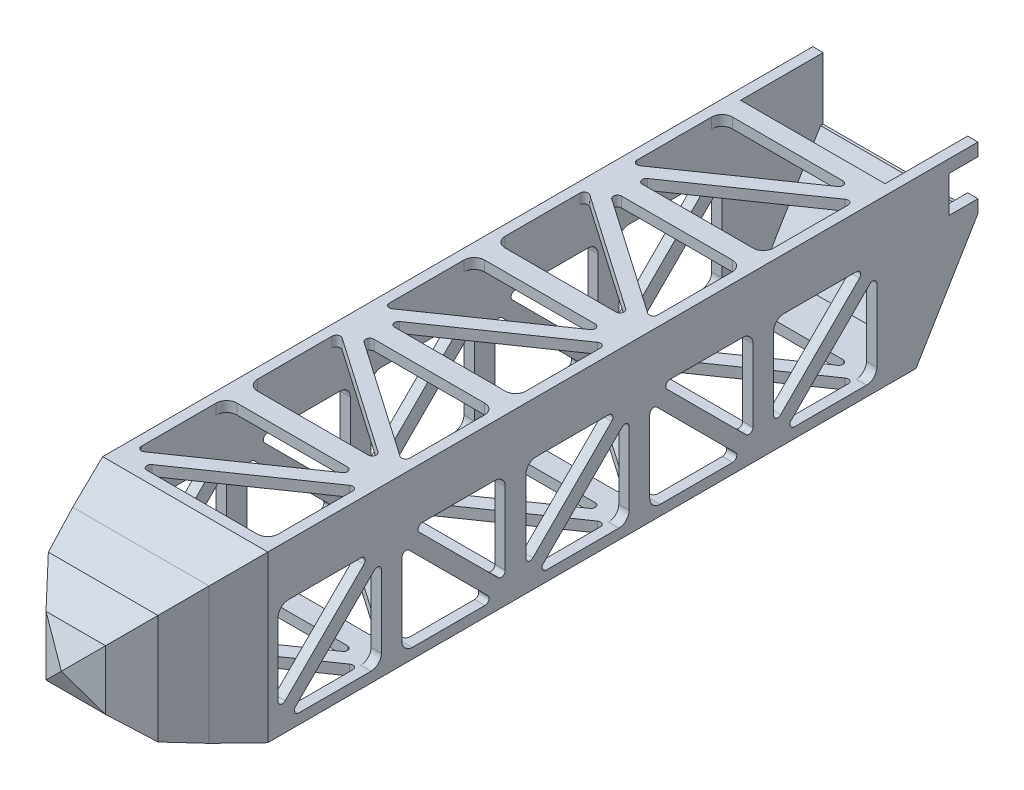
SolidWorks part; units mm, degrees
material "Balsa"
ref_plane "Front Plane" through (0, 0, 0) normal (0, 0, 1) x (1, 0, 0)
ref_plane "Top Plane" through (0, 0, 0) normal (0, 1, 0) x (1, 0, 0)
ref_plane "Right Plane" through (0, 0, 0) normal (1, 0, 0) x (0, 0, -1)
sketch "Sketch1" plane through (0, 0, 0) normal (0, 0, 1) x (1, 0, 0)
  line L1 (-50.8, -50.8) -> (50.8, -50.8)
  line L2 (-50.8, -50.8) -> (-50.8, 50.8)
  line L3 (-50.8, 50.8) -> (50.8, 50.8)
  line L4 (50.8, -50.8) -> (50.8, 50.8)
  line L5 (-50.8, -50.8) -> (50.8, 50.8) construction
  line L6 (-50.8, 50.8) -> (50.8, -50.8) construction
  point P0 (0, 0)
  dimension "D1" = 101.6
extrude "Boss-Extrude1" add sketch "Sketch1" along normal blind 436.88 contours L2 L1 L4 L3
ref_plane "Plane1" through (0, 0, 464.1566) normal (0, 0, 1) x (1, 0, 0)
sketch "Sketch3" plane through (0, 0, 464.1566) normal (0, 0, 1) x (1, 0, 0)
  line L1 (-41.9373, -41.9373) -> (41.9373, -41.9373)
  line L2 (-41.9373, -41.9373) -> (-41.9373, 41.9373)
  line L3 (-41.9373, 41.9373) -> (41.9373, 41.9373)
  line L4 (41.9373, -41.9373) -> (41.9373, 41.9373)
  line L5 (-41.9373, -41.9373) -> (41.9373, 41.9373) construction
  line L6 (-41.9373, 41.9373) -> (41.9373, -41.9373) construction
  point P0 (0, 0)
  dimension "D1" = 83.8746
  dimension "D2" = 83.8746
sketch "Sketch5" plane through (0, 0, 436.88) normal (0, 0, 1) x (1, 0, 0)
  line L0 (50.8, -50.8) -> (50.8, 50.8) construction
  line L1 (-50.8, 50.8) -> (50.8, 50.8) construction
  line L2 (-50.8, -50.8) -> (-50.8, 50.8) construction
  line L3 (-50.8, -50.8) -> (50.8, -50.8) construction
  line L4 (50.8, -50.8) -> (50.8, 50.8)
  line L5 (-50.8, 50.8) -> (50.8, 50.8)
  line L6 (-50.8, -50.8) -> (-50.8, 50.8)
  line L7 (-50.8, -50.8) -> (50.8, -50.8)
  dimension "D1" = 101.6
  dimension "D2" = 101.6
loft "Loft2" add profiles "Sketch5", "Sketch3" connector at (-50.8, 50.8, 436.88) connector at (-41.9373, 41.9373, 464.1566)
ref_plane "Plane2" through (0, 0, 487.3594) normal (0, 0, 1) x (1, 0, 0)
sketch "Sketch6" plane through (0, 0, 487.3594) normal (0, 0, 1) x (1, 0, 0)
  line L1 (-33.716, -33.716) -> (33.716, -33.716)
  line L2 (-33.716, -33.716) -> (-33.716, 33.716)
  line L3 (-33.716, 33.716) -> (33.716, 33.716)
  line L4 (33.716, -33.716) -> (33.716, 33.716)
  line L5 (-33.716, -33.716) -> (33.716, 33.716) construction
  line L6 (-33.716, 33.716) -> (33.716, -33.716) construction
  point P0 (0, 0)
loft "Loft3" add profiles "Sketch3<6>", "Sketch6" connector at (-41.9373, 41.9373, 464.1566) connector at (-33.716, 33.716, 487.3594)
sketch "Sketch3<6>" plane through (0, 0, 464.1566) normal (0, 0, 1) x (1, 0, 0) same geometry as "Sketch3"
ref_plane "Plane3" through (0, 0, 504.2173) normal (0, 0, 1) x (1, 0, 0)
sketch "Sketch7" plane through (0, 0, 504.2173) normal (0, 0, 1) x (1, 0, 0)
  line L5 (-41.9373, -41.9373) -> (41.9373, 41.9373) construction
  line L6 (-18.3041, -18.3041) -> (18.3041, -18.3041)
  line L8 (-18.3041, -18.3041) -> (-18.3041, 18.3041)
  line L9 (-18.3041, 18.3041) -> (18.3041, 18.3041)
  line L10 (18.3041, -18.3041) -> (18.3041, 18.3041)
  line L11 (-18.3041, -18.3041) -> (18.3041, 18.3041) construction
  line L12 (-18.3041, 18.3041) -> (18.3041, -18.3041) construction
  point P1 (0, 0)
loft "Loft4" add profiles "Sketch6<4>", "Sketch7" connector at (33.716, 33.716, 487.3594) connector at (18.3041, 18.3041, 504.2173)
sketch "Sketch6<4>" plane through (0, 0, 487.3594) normal (0, 0, 1) x (1, 0, 0) same geometry as "Sketch6"
sketch3d "3DSketch1" plane through (0, 0, 0) normal (0, 0, 1) x (1, 0, 0)
  dimension "D1" = 8.8627
sketch "Sketch8" plane through (0, 0, 513.08) normal (0, 0, 1) x (1, 0, 0)
  point P0 (0, 0)
loft "Loft5" add profiles "Sketch8", "Sketch7<5>"
sketch "Sketch7<5>" plane through (0, 0, 504.2173) normal (0, 0, 1) x (1, 0, 0) same geometry as "Sketch7"
shell "Shell1" thickness 6.35 removed face at (0, 0, 0)
sketch "Sketch10" plane through (50.8, 0, 0) normal (1, 0, 0) x (0, 0, -1)
  line L0 (-436.88, 50.8) -> (0, 50.8) construction
  line L3 (0, 50.8) -> (-68.9584, 50.8)
  line L4 (-68.9584, -50.8) -> (-68.9584, 50.8)
  line L5 (0, 50.8) -> (0, 12.7)
  line L6 (0, -50.8) -> (-38.1, -50.8)
  line L7 (0, 12.7) -> (-38.1, -50.8)
  line L8 (0, 12.7) -> (0, -50.8)
  line M16 (0, -50.8) -> (0, 50.8)
  line M19 (-436.88, -50.8) -> (0, -50.8)
  dimension "D1" = 38.1
  dimension "D2" = 38.1
  dimension "D3" = 63.5
extrude "Cut-Extrude2" cut sketch "Sketch10" against normal through all contours L7 M16 M19 region at (50.8, -29.6333, 12.7)
sketch "Sketch11" plane through (50.8, 0, 0) normal (1, 0, 0) x (0, 0, -1)
  line L0 (-38.1, -50.8) -> (-39.6875, -50.8)
  line L1 (-436.88, -50.8) -> (-38.1, -50.8) construction
  line L2 (0, 50.8) -> (-1.5875, 50.8)
  line L3 (-436.88, 50.8) -> (0, 50.8) construction
  line L4 (-1.5875, 50.8) -> (-1.5875, 12.7)
  line L5 (0, 50.8) -> (0, 12.7)
  line L6 (-1.5875, 12.7) -> (-39.6875, -50.8)
  line L7 (0, 12.7) -> (-38.1, -50.8)
  dimension "D1" = 1.5875
  dimension "D2" = 1.5875
extrude "Boss-Extrude2" add sketch "Sketch11" against normal blind 101.6
sketch "Sketch12" plane through (0, 0, 0) normal (0, 0, -1) x (-1, 0, 0)
  line L0 (-50.8, 50.8) -> (-44.45, 50.8)
  line L1 (50.8, 50.8) -> (-50.8, 50.8) construction
  line L2 (50.8, 12.7) -> (-50.8, 12.7) construction
  line L3 (-44.45, 50.8) -> (44.45, 50.8)
  line L4 (-44.45, 50.8) -> (-44.45, 12.7)
  line L5 (-44.45, 12.7) -> (44.45, 12.7)
  line L6 (44.45, 50.8) -> (44.45, 12.7)
  line M7 (-50.8, 12.7) -> (50.8, 12.7)
  line M9 (50.8, 50.8) -> (-50.8, 50.8)
  dimension "D1" = 6.35
  dimension "D2" = 88.9
extrude "Cut-Extrude3" cut sketch "Sketch12" against normal blind 50.8 contours L6 L4 M9 M7 region at (0, 31.75, 0)
sketch "Sketch15" plane through (50.8, 0, 0) normal (1, 0, 0) x (0, 0, -1)
  line L0 (0, 12.7) -> (0, 50.8) construction
  line L1 (0, 42.926) -> (-17.78, 42.926)
  line L2 (0, 42.926) -> (0, 20.574)
  line L3 (0, 20.574) -> (-17.78, 20.574)
  line L4 (-17.78, 42.926) -> (-17.78, 20.574)
  line L5 (-436.88, 50.8) -> (0, 50.8) construction
  dimension "D1" = 17.78
  dimension "D2" = 22.352
  dimension "D3" = 7.874
extrude "Cut-Extrude5" cut sketch "Sketch15" against normal up to surface (6.35 mm away)
sketch "Sketch16" plane through (50.8, 0, 0) normal (1, 0, 0) x (0, 0, -1)
  line L0 (-436.88, -50.8) -> (-436.88, 50.8) construction
  line L1 (-424.18, 19.05) -> (-379.5121, 19.05)
  line L2 (-430.53, 12.7) -> (-430.53, -31.9679)
  line L3 (-418.0479, -44.45) -> (-373.38, -44.45)
  line L4 (-367.03, 6.5679) -> (-367.03, -38.1)
  line L5 (-436.88, -50.8) -> (-38.1, -50.8) construction
  line L6 (-354.33, 6.5679) -> (-354.33, -38.1)
  line L7 (-341.8479, 19.05) -> (-297.18, 19.05)
  line L8 (-290.83, 12.7) -> (-290.83, -31.9679)
  line L9 (-347.98, -44.45) -> (-303.3121, -44.45)
  line L10 (-278.13, 12.7) -> (-278.13, -31.9679)
  line L11 (-271.78, 19.05) -> (-227.1121, 19.05)
  line L12 (-214.63, 6.5679) -> (-214.63, -38.1)
  line L13 (-265.6479, -44.45) -> (-220.98, -44.45)
  line L14 (-201.93, 6.5679) -> (-201.93, -38.1)
  line L15 (-189.4479, 19.05) -> (-144.78, 19.05)
  line L16 (-138.43, 12.7) -> (-138.43, -31.9679)
  line L17 (-195.58, -44.45) -> (-150.9121, -44.45)
  line L18 (-125.73, 12.7) -> (-125.73, -31.9679)
  line L19 (-119.38, 19.05) -> (-74.7121, 19.05)
  line L20 (-62.23, 6.5679) -> (-62.23, -38.1)
  line L21 (-113.2479, -44.45) -> (-68.58, -44.45)
  line L22 (-377.7161, 14.7139) -> (-426.1939, -33.7639)
  line L23 (-419.8439, -40.1139) -> (-371.3661, 8.3639)
  line L24 (-349.9939, 8.3639) -> (-301.5161, -40.1139)
  line L25 (-343.6439, 14.7139) -> (-295.1661, -33.7639)
  line L26 (-273.7939, -33.7639) -> (-225.3161, 14.7139)
  line L27 (-218.9661, 8.3639) -> (-267.4439, -40.1139)
  line L28 (-197.5939, 8.3639) -> (-149.1161, -40.1139)
  line L29 (-142.7661, -33.7639) -> (-191.2439, 14.7139)
  line L30 (-121.3939, -33.7639) -> (-72.9161, 14.7139)
  line L31 (-66.5661, 8.3639) -> (-115.0439, -40.1139)
  arc A0 (-430.53, -38.1) -> (-424.18, -44.45) centre (-424.18, -38.1) ccw
  arc A1 (-373.38, -44.45) -> (-367.03, -38.1) centre (-373.38, -38.1) ccw
  arc A2 (-373.38, 19.05) -> (-367.03, 12.7) centre (-373.38, 12.7) cw
  arc A3 (-424.18, 19.05) -> (-430.53, 12.7) centre (-424.18, 12.7) ccw
  arc A4 (-347.98, 19.05) -> (-354.33, 12.7) centre (-347.98, 12.7) ccw
  arc A5 (-354.33, -38.1) -> (-347.98, -44.45) centre (-347.98, -38.1) ccw
  arc A6 (-297.18, 19.05) -> (-290.83, 12.7) centre (-297.18, 12.7) cw
  arc A7 (-297.18, -44.45) -> (-290.83, -38.1) centre (-297.18, -38.1) ccw
  arc A8 (-271.78, 19.05) -> (-278.13, 12.7) centre (-271.78, 12.7) ccw
  arc A9 (-278.13, -38.1) -> (-271.78, -44.45) centre (-271.78, -38.1) ccw
  arc A10 (-220.98, 19.05) -> (-214.63, 12.7) centre (-220.98, 12.7) cw
  arc A11 (-220.98, -44.45) -> (-214.63, -38.1) centre (-220.98, -38.1) ccw
  arc A12 (-195.58, 19.05) -> (-201.93, 12.7) centre (-195.58, 12.7) ccw
  arc A13 (-201.93, -38.1) -> (-195.58, -44.45) centre (-195.58, -38.1) ccw
  arc A14 (-144.78, 19.05) -> (-138.43, 12.7) centre (-144.78, 12.7) cw
  arc A15 (-144.78, -44.45) -> (-138.43, -38.1) centre (-144.78, -38.1) ccw
  arc A16 (-119.38, 19.05) -> (-125.73, 12.7) centre (-119.38, 12.7) ccw
  arc A17 (-125.73, -38.1) -> (-119.38, -44.45) centre (-119.38, -38.1) ccw
  arc A18 (-68.58, 19.05) -> (-62.23, 12.7) centre (-68.58, 12.7) cw
  arc A19 (-68.58, -44.45) -> (-62.23, -38.1) centre (-68.58, -38.1) ccw
  arc A20 (-74.7121, 19.05) -> (-72.9161, 14.7139) centre (-74.7121, 16.51) cw
  arc A21 (-66.5661, 8.3639) -> (-62.23, 6.5679) centre (-64.77, 6.5679) cw
  arc A22 (-115.0439, -40.1139) -> (-113.2479, -44.45) centre (-113.2479, -41.91) ccw
  arc A23 (-121.3939, -33.7639) -> (-125.73, -31.9679) centre (-123.19, -31.9679) cw
  arc A24 (-150.9121, -44.45) -> (-149.1161, -40.1139) centre (-150.9121, -41.91) ccw
  arc A25 (-142.7661, -33.7639) -> (-138.43, -31.9679) centre (-140.97, -31.9679) ccw
  arc A26 (-189.4479, 19.05) -> (-191.2439, 14.7139) centre (-189.4479, 16.51) ccw
  arc A27 (-197.5939, 8.3639) -> (-201.93, 6.5679) centre (-199.39, 6.5679) ccw
  arc A28 (-227.1121, 19.05) -> (-225.3161, 14.7139) centre (-227.1121, 16.51) cw
  arc A29 (-218.9661, 8.3639) -> (-214.63, 6.5679) centre (-217.17, 6.5679) cw
  arc A30 (-265.6479, -44.45) -> (-267.4439, -40.1139) centre (-265.6479, -41.91) cw
  arc A31 (-278.13, -31.9679) -> (-273.7939, -33.7639) centre (-275.59, -31.9679) ccw
  arc A32 (-303.3121, -44.45) -> (-301.5161, -40.1139) centre (-303.3121, -41.91) ccw
  arc A33 (-290.83, -31.9679) -> (-295.1661, -33.7639) centre (-293.37, -31.9679) cw
  arc A34 (-341.8479, 19.05) -> (-343.6439, 14.7139) centre (-341.8479, 16.51) ccw
  arc A35 (-349.9939, 8.3639) -> (-354.33, 6.5679) centre (-351.79, 6.5679) ccw
  arc A36 (-367.03, 6.5679) -> (-371.3661, 8.3639) centre (-369.57, 6.5679) ccw
  arc A37 (-418.0479, -44.45) -> (-419.8439, -40.1139) centre (-418.0479, -41.91) cw
  arc A38 (-377.7161, 14.7139) -> (-379.5121, 19.05) centre (-379.5121, 16.51) ccw
  arc A39 (-426.1939, -33.7639) -> (-430.53, -31.9679) centre (-427.99, -31.9679) cw
  point P12 (-367.03, -44.45)
  point P15 (-367.03, 19.05)
  point P18 (-430.53, 19.05)
  dimension "D1" = 6.35
  dimension "D5" = 6.35
  dimension "D7" = 2.54
  dimension "D2" = 6.35
  dimension "D3" = 63.5
  dimension "D4" = 63.5
  dimension "D6" = 5
extrude "Cut-Extrude6" cut sketch "Sketch16" against normal up to surface (101.6 mm away) contours L1 A3 L2 L22 | L3 A1 L4 L23 | L6 A5 L9 L24 | A6 L7 L25 L8 | L11 A8 L10 L26 | L13 A11 L12 L27 | L14 A13 L17 L28 | A14 L15 L29 L16 | L21 A19 L20 L31 | L19 A16 L18 L30 region at (50.8, -0.0083, 411.4717) region at (50.8, -25.3917, 386.0883) region at (50.8, -25.3917, 335.2717) region at (50.8, -0.0083, 309.8883) region at (50.8, -0.0083, 259.0717) region at (50.8, -25.3917, 233.6883) region at (50.8, -25.3917, 182.8717) region at (50.8, -0.0083, 157.4883) region at (50.8, -0.0083, 106.6717) region at (50.8, -25.3917, 81.2883) up to face at (-50.8, 2.54, 182.372)
sketch "Sketch17" plane through (0, 50.8, 0) normal (0, 1, 0) x (1, 0, 0)
  line L0 (50.8, -436.88) -> (50.8, 0) construction
  line L1 (38.1, -430.53) -> (-22.2093, -430.53)
  line L2 (44.45, -424.18) -> (44.45, -382.8539)
  line L3 (22.2093, -367.03) -> (-38.1, -367.03)
  line L4 (-44.45, -414.7061) -> (-44.45, -373.38)
  line L5 (-50.8, -436.88) -> (50.8, -436.88) construction
  line L6 (-50.8, -436.88) -> (-50.8, 0) construction
  line L7 (44.45, -344.747) -> (44.45, -303.4209)
  line L8 (22.2093, -360.5709) -> (-38.1, -360.5709)
  line L9 (-44.45, -354.2209) -> (-44.45, -306.6045)
  line L11 (44.45, -284.2618) -> (44.45, -236.6454)
  line L12 (38.1, -290.6118) -> (-32.7601, -290.6118)
  line L13 (-44.45, -281.0782) -> (-44.45, -233.4618)
  line L14 (37.5789, -227.1118) -> (-38.1, -227.1118)
  line L15 (44.45, -211.1191) -> (44.45, -163.5027)
  line L16 (32.7601, -220.6527) -> (-38.1, -220.6527)
  line L17 (-44.45, -214.3027) -> (-44.45, -166.6863)
  line L19 (44.45, -144.3436) -> (44.45, -98.3913)
  line L20 (38.1, -150.6936) -> (-37.3066, -150.6936)
  line L21 (-44.45, -139.4958) -> (-44.45, -93.5436)
  line L22 (29.9688, -87.1936) -> (-38.1, -87.1936)
  line L23 (-36.6606, -418.7874) -> (25.0348, -376.0751)
  line L24 (38.1, -367.03) -> (44.45, -373.38)
  line L25 (-25.0348, -421.4849) -> (36.6606, -378.7726)
  line L26 (36.6606, -348.8283) -> (-31.4146, -301.6993)
  line L27 (-41.8325, -305.233) -> (25.0348, -351.5257)
  line L28 (-33.7096, -287.5723) -> (41.8325, -235.2739)
  line L29 (38.5284, -226.8152) -> (-41.8325, -282.4497)
  line L30 (33.7096, -217.6132) -> (-41.8325, -165.3148)
  line L31 (-31.4146, -161.7811) -> (41.8325, -212.4906)
  line L32 (-38.7524, -151.1452) -> (40.4642, -96.303)
  line L33 (31.4146, -91.822) -> (-40.4642, -141.5842)
  line L35 (38.1, -157.1527) -> (-37.3066, -157.1527) [skipped]
  line L36 (38.1, -157.1527) -> (35.6588, -123.3001)
  line L37 (-29.9688, -157.1527) -> (38.1, -157.1527)
  line L38 (-29.9688, -297.0709) -> (38.1, -297.0709)
  line L39 (38.1, -297.0709) -> (-36.5494, -297.0709) [skipped]
  arc A0 (44.45, -373.38) -> (38.1, -367.03) centre (38.1, -373.38) ccw
  arc A1 (38.1, -430.53) -> (44.45, -424.18) centre (38.1, -424.18) ccw
  arc A2 (-38.1, -430.53) -> (-44.45, -424.18) centre (-38.1, -424.18) cw
  arc A3 (-38.1, -367.03) -> (-44.45, -373.38) centre (-38.1, -373.38) ccw
  arc A4 (38.1, -360.5709) -> (44.45, -354.2209) centre (38.1, -354.2209) ccw
  arc A5 (44.45, -303.4209) -> (38.1, -297.0709) centre (38.1, -303.4209) ccw
  arc A6 (-38.1, -360.5709) -> (-44.45, -354.2209) centre (-38.1, -354.2209) cw
  arc A7 (-38.1, -297.0709) -> (-44.45, -303.4209) centre (-38.1, -303.4209) ccw
  arc A8 (38.1, -290.6118) -> (44.45, -284.2618) centre (38.1, -284.2618) ccw
  arc A9 (44.45, -233.4618) -> (38.1, -227.1118) centre (38.1, -233.4618) ccw
  arc A10 (-38.1, -290.6118) -> (-44.45, -284.2618) centre (-38.1, -284.2618) cw
  arc A11 (-38.1, -227.1118) -> (-44.45, -233.4618) centre (-38.1, -233.4618) ccw
  arc A12 (38.1, -220.6527) -> (44.45, -214.3027) centre (38.1, -214.3027) ccw
  arc A13 (44.45, -163.5027) -> (38.1, -157.1527) centre (38.1, -163.5027) ccw
  arc A14 (-38.1, -220.6527) -> (-44.45, -214.3027) centre (-38.1, -214.3027) cw
  arc A16 (38.1, -150.6936) -> (44.45, -144.3436) centre (38.1, -144.3436) ccw
  arc A17 (44.45, -93.5436) -> (38.1, -87.1936) centre (38.1, -93.5436) ccw
  arc A18 (-38.1, -150.6936) -> (-44.45, -144.3436) centre (-38.1, -144.3436) cw
  arc A19 (-38.1, -87.1936) -> (-44.45, -93.5436) centre (-38.1, -93.5436) ccw
  arc A20 (-40.4642, -141.5842) -> (-44.45, -139.4958) centre (-41.91, -139.4958) cw
  arc A21 (31.4146, -91.822) -> (29.9688, -87.1936) centre (29.9688, -89.7336) ccw
  arc A22 (40.4642, -96.303) -> (44.45, -98.3913) centre (41.91, -98.3913) cw
  arc A23 (-38.7524, -151.1452) -> (-37.3066, -150.6936) centre (-37.3066, -153.2336) ccw
  arc A25 (-41.8325, -165.3148) -> (-44.45, -166.6863) centre (-42.7819, -166.6863) ccw
  arc A26 (44.45, -211.1191) -> (41.8325, -212.4906) centre (42.7819, -211.1191) cw
  arc A27 (33.7096, -217.6132) -> (32.7601, -220.6527) centre (32.7601, -218.9846) cw
  arc A28 (37.5789, -227.1118) -> (38.5284, -226.8152) centre (37.5789, -225.4437) cw
  arc A29 (41.8325, -235.2739) -> (44.45, -236.6454) centre (42.7819, -236.6454) cw
  arc A30 (-32.7601, -290.6118) -> (-33.7096, -287.5723) centre (-32.7601, -288.9437) cw
  arc A31 (-41.8325, -282.4497) -> (-44.45, -281.0782) centre (-42.7819, -281.0782) cw
  arc A32 (-44.45, -306.6045) -> (-41.8325, -305.233) centre (-42.7819, -306.6045) cw
  arc A34 (44.45, -344.747) -> (36.6606, -348.8283) centre (39.4861, -344.747) cw
  arc A35 (22.2093, -360.5709) -> (25.0348, -351.5257) centre (22.2093, -355.607) ccw
  arc A36 (44.45, -382.8539) -> (36.6606, -378.7726) centre (39.4861, -382.8539) ccw
  arc A37 (25.0348, -376.0751) -> (22.2093, -367.03) centre (22.2093, -371.9939) ccw
  arc A38 (-44.45, -414.7061) -> (-36.6606, -418.7874) centre (-39.4861, -414.7061) ccw
  arc A39 (-22.2093, -430.53) -> (-25.0348, -421.4849) centre (-22.2093, -425.5661) cw
  arc A40 (-38.1, -157.1527) -> (-44.45, -163.5027) centre (-38.1, -163.5027) ccw [skipped]
  arc A41 (-31.4146, -161.7811) -> (-29.9688, -157.1527) centre (-29.9688, -159.6927) cw
  arc A42 (-31.4146, -301.6993) -> (-29.9688, -297.0709) centre (-29.9688, -299.6109) cw
  point P16 (-44.45, -430.53)
  point P19 (-44.45, -367.03)
  dimension "D1" = 6.35
  dimension "D5" = 6.35
  dimension "D7" = 2.54
  dimension "D2" = 6.35
  dimension "D4" = 63.5
  dimension "D6" = 5
  dimension "D8" = 2.54
  dimension "D9" = 2.54
  dimension "D3" = 6.35
sketch "Sketch18" plane through (0, 50.8, 0) normal (0, 1, 0) x (1, 0, 0)
  line L0 (-50.8, -436.88) -> (-50.8, 0) construction
  line L1 (38.1, -430.53) -> (-29.9688, -430.53)
  line L2 (44.45, -424.18) -> (44.45, -378.2278)
  line L3 (29.9688, -367.03) -> (-38.1, -367.03)
  line L4 (-44.45, -419.3322) -> (-44.45, -373.38)
  line L5 (50.8, -436.88) -> (50.8, 0) construction
  line L6 (-50.8, -436.88) -> (50.8, -436.88) construction
  line L7 (-40.4642, -299.9394) -> (31.4146, -349.7016)
  line L8 (-38.1, -354.33) -> (29.9688, -354.33)
  line L9 (-44.45, -347.98) -> (-44.45, -302.0278)
  line L10 (-29.9688, -290.83) -> (38.1, -290.83)
  line L11 (44.45, -343.1322) -> (44.45, -297.18)
  line L12 (40.4642, -345.2206) -> (-31.4146, -295.4584)
  line L13 (31.4146, -371.6584) -> (-40.4642, -421.4206)
  line L14 (-31.4146, -425.9016) -> (40.4642, -376.1394)
  line L15 (38.1, -278.13) -> (-29.9688, -278.13)
  line L16 (44.45, -271.78) -> (44.45, -225.8278)
  line L17 (-31.4146, -273.5016) -> (40.4642, -223.7394)
  line L18 (31.4146, -219.2584) -> (-40.4642, -269.0206)
  line L19 (29.9688, -214.63) -> (-38.1, -214.63)
  line L20 (-44.45, -266.9322) -> (-44.45, -220.98)
  line L21 (-38.1, -201.93) -> (29.9688, -201.93)
  line L22 (-44.45, -195.58) -> (-44.45, -149.6278)
  line L23 (-40.4642, -147.5394) -> (31.4146, -197.3016)
  line L24 (40.4642, -192.8206) -> (-31.4146, -143.0584)
  line L25 (-29.9688, -138.43) -> (38.1, -138.43)
  line L26 (44.45, -190.7322) -> (44.45, -144.78)
  line L27 (38.1, -125.73) -> (-29.9688, -125.73)
  line L28 (44.45, -119.38) -> (44.45, -73.4278)
  line L29 (-31.4146, -121.1016) -> (40.4642, -71.3394)
  line L30 (31.4146, -66.8584) -> (-40.4642, -116.6206)
  line L31 (29.9688, -62.23) -> (-38.1, -62.23)
  line L32 (-44.45, -114.5322) -> (-44.45, -68.58)
  line L39 (-38.1, -49.53) -> (29.9688, -49.53) [skipped]
  line L40 (-40.4642, 4.8606) -> (31.4146, -44.9016) [skipped]
  line L41 (-44.45, -43.18) -> (-44.45, 2.7722) [skipped]
  line L42 (40.4642, -40.4206) -> (-31.4146, 9.3416) [skipped]
  line L43 (-29.9688, 13.97) -> (38.1, 13.97) [skipped]
  line L44 (44.45, -38.3322) -> (44.45, 7.62) [skipped]
  arc A0 (38.1, -430.53) -> (44.45, -424.18) centre (38.1, -424.18) ccw
  arc A3 (-38.1, -367.03) -> (-44.45, -373.38) centre (-38.1, -373.38) ccw
  arc A4 (-38.1, -354.33) -> (-44.45, -347.98) centre (-38.1, -347.98) cw
  arc A6 (38.1, -290.83) -> (44.45, -297.18) centre (38.1, -297.18) cw
  arc A8 (44.45, -343.1322) -> (40.4642, -345.2206) centre (41.91, -343.1322) cw
  arc A9 (-29.9688, -290.83) -> (-31.4146, -295.4584) centre (-29.9688, -293.37) ccw
  arc A10 (-44.45, -302.0278) -> (-40.4642, -299.9394) centre (-41.91, -302.0278) cw
  arc A11 (29.9688, -354.33) -> (31.4146, -349.7016) centre (29.9688, -351.79) ccw
  arc A12 (44.45, -378.2278) -> (40.4642, -376.1394) centre (41.91, -378.2278) ccw
  arc A13 (29.9688, -367.03) -> (31.4146, -371.6584) centre (29.9688, -369.57) cw
  arc A14 (-29.9688, -430.53) -> (-31.4146, -425.9016) centre (-29.9688, -427.99) cw
  arc A15 (-44.45, -419.3322) -> (-40.4642, -421.4206) centre (-41.91, -419.3322) ccw
  arc A16 (-29.9688, -278.13) -> (-31.4146, -273.5016) centre (-29.9688, -275.59) cw
  arc A17 (38.1, -278.13) -> (44.45, -271.78) centre (38.1, -271.78) ccw
  arc A18 (44.45, -225.8278) -> (40.4642, -223.7394) centre (41.91, -225.8278) ccw
  arc A19 (-44.45, -266.9322) -> (-40.4642, -269.0206) centre (-41.91, -266.9322) ccw
  arc A20 (29.9688, -214.63) -> (31.4146, -219.2584) centre (29.9688, -217.17) cw
  arc A21 (-38.1, -214.63) -> (-44.45, -220.98) centre (-38.1, -220.98) ccw
  arc A22 (29.9688, -201.93) -> (31.4146, -197.3016) centre (29.9688, -199.39) ccw
  arc A23 (-38.1, -201.93) -> (-44.45, -195.58) centre (-38.1, -195.58) cw
  arc A24 (-44.45, -149.6278) -> (-40.4642, -147.5394) centre (-41.91, -149.6278) cw
  arc A25 (-29.9688, -138.43) -> (-31.4146, -143.0584) centre (-29.9688, -140.97) ccw
  arc A26 (44.45, -190.7322) -> (40.4642, -192.8206) centre (41.91, -190.7322) cw
  arc A27 (38.1, -138.43) -> (44.45, -144.78) centre (38.1, -144.78) cw
  arc A28 (-29.9688, -125.73) -> (-31.4146, -121.1016) centre (-29.9688, -123.19) cw
  arc A29 (38.1, -125.73) -> (44.45, -119.38) centre (38.1, -119.38) ccw
  arc A30 (44.45, -73.4278) -> (40.4642, -71.3394) centre (41.91, -73.4278) ccw
  arc A31 (-44.45, -114.5322) -> (-40.4642, -116.6206) centre (-41.91, -114.5322) ccw
  arc A32 (29.9688, -62.23) -> (31.4146, -66.8584) centre (29.9688, -64.77) cw
  arc A33 (-38.1, -62.23) -> (-44.45, -68.58) centre (-38.1, -68.58) ccw
  arc A40 (29.9688, -49.53) -> (31.4146, -44.9016) centre (29.9688, -46.99) ccw [skipped]
  arc A41 (-44.45, 2.7722) -> (-40.4642, 4.8606) centre (-41.91, 2.7722) cw [skipped]
  arc A42 (-38.1, -49.53) -> (-44.45, -43.18) centre (-38.1, -43.18) cw [skipped]
  arc A43 (-29.9688, 13.97) -> (-31.4146, 9.3416) centre (-29.9688, 11.43) ccw [skipped]
  arc A44 (38.1, 13.97) -> (44.45, 7.62) centre (38.1, 7.62) cw [skipped]
  arc A45 (44.45, -38.3322) -> (40.4642, -40.4206) centre (41.91, -38.3322) cw [skipped]
  point P12 (44.45, -430.53)
  point P15 (44.45, -367.03)
  point P28 (44.45, -354.33)
  point P31 (44.45, -290.83)
  dimension "D1" = 6.35
  dimension "D5" = 6.35
  dimension "D2" = 6.35
  dimension "D4" = 63.5
  dimension "D3" = 6.35
  dimension "D10" = 6.35
  dimension "D11" = 2.54
  dimension "D6" = 12.7
  dimension "D8" = 6.35
  dimension "D9" = 6.35
  dimension "D12" = 3
extrude "Cut-Extrude9" cut sketch "Sketch18" against normal up to surface (101.6 mm away) up to face at (0, -50.8, 237.49)
ref_plane "Plane4" through (0, 38.1, 0) normal (0, 1, 0) x (1, 0, 0)
ref_plane "Plane5" through (0, -4.6068, 436.295) normal (0, -0.0106, 0.9999) x (1, 0, 0)
equation "\"Fuse_Diam\"= 4"
equation "\"D2@Sketch1\"=\"Fuse_Diam\""
equation "\"D1@Sketch1\"=\"Fuse_Diam\""
equation "\"Magic Line\"= 3 / ( cos ( 18 ) + cos ( 2 * 18 ) + cos ( 3 * 18 ) + cos ( 4 * 18 ) )"
equation "\"Second Stage Cone\"= 3.30215"
equation "\"D1@Sketch3\"=\"Second Stage Cone\""
equation "\"D2@Sketch3\"=\"Second Stage Cone\""
equation "\"Thick\"=0.25"
equation "\"D1@Sketch12\"=\"Thick\""
equation "\"D1@Shell1\"=\"Thick\""
equation "\"attachment\"=3.5"
equation "\"D2@Sketch12\"=\"attachment\""
equation "\"D2@Sketch16\"=\"Thick\""
equation "\"D1@Sketch16\"=0.25in"
equation "\"D1@Sketch17\"=\"Thick\""
equation "\"D2@Sketch17\"=\"Thick\""
equation "\"D3@Sketch17\"=\"Thick\""
equation "\"D1@Sketch18\"=\"Thick\""
equation "\"D2@Sketch18\"=\"Thick\""
